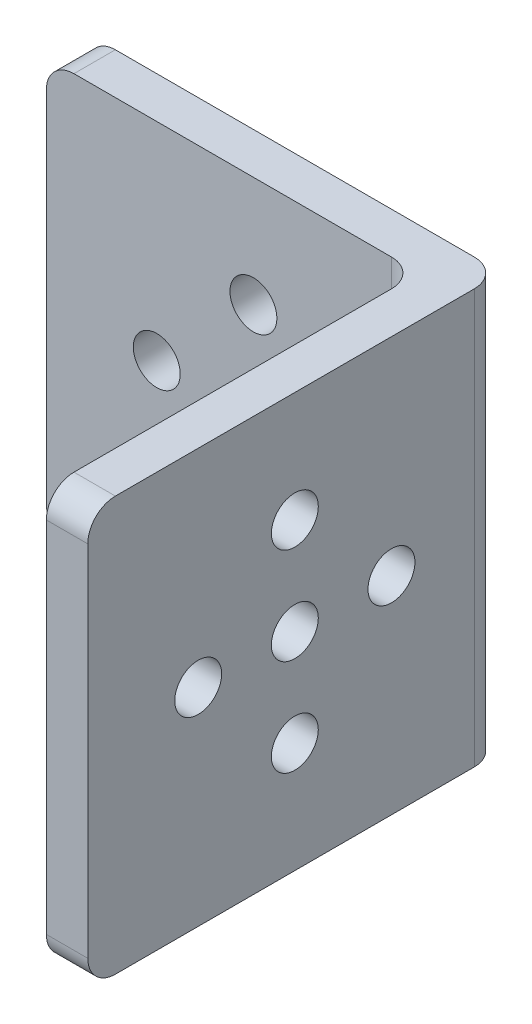
SolidWorks part; units mm, degrees
ref_plane "Front Plane" through (0, 0, 0) normal (0, 0, 1) x (1, 0, 0)
ref_plane "Top Plane" through (0, 0, 0) normal (0, 1, 0) x (1, 0, 0)
ref_plane "Right Plane" through (0, 0, 0) normal (1, 0, 0) x (0, 0, -1)
sketch "Sketch1" plane through (0, 0, 0) normal (0, 0, 1) x (1, 0, 0)
  line L0 (12, 15) -> (12, -15)
  line L9 (-15, -15) -> (15, -15)
  line L10 (-15, -15) -> (-15, 15)
  line L11 (-15, 15) -> (15, 15)
  line L12 (15, -15) -> (15, 15)
  line L13 (-15, -15) -> (15, 15) construction
  line L14 (-15, 15) -> (15, -15) construction
  point P0 (0, 0)
  dimension "D1" = 30
  dimension "D2" = 3
extrude "Boss-Extrude1" add sketch "Sketch1" along normal blind 3 contours L11 L10 L9 L0 region at (-1.5, 0, 0)
extrude "Boss-Extrude2" add sketch "Sketch1<3>" along normal blind 30 contours L9 L12 L11 L0 region at (13.5, 0, 0)
sketch "Sketch1<3>" plane through (0, 0, 0) normal (0, 0, 1) x (1, 0, 0) same geometry as "Sketch1"
sketch "Sketch2" plane through (0, 0, 3) normal (0, 0, 1) x (1, 0, 0)
  circle A0 centre (0, 0) radius 1.5
  circle A1 centre (0, 0) radius 7
  circle A2 centre (0, 7) radius 1.5
  circle A3 centre (7, 0) radius 1.5
  circle A4 centre (0, -7) radius 1.5
  circle A5 centre (-7, 0) radius 1.5
  dimension "D1" = 3
  dimension "D2" = 14
  dimension "D3" = 3
  dimension "D4" = 3
  dimension "D5" = 3
  dimension "D6" = 3
hole_wizard "M3 Clearance Hole1" positions "3DSketch1" profile "Sketch3" hole size "M3" standard "ISO" end condition up to next
sketch3d "3DSketch1"
  point P0 (0, 7, 3)
  point P3 (-7, 0, 3)
  point P6 (7, 0, 3)
  point P9 (0, -7, 3)
  point P13 (0, 0, 0)
  point P16 (0, 0, 3)
sketch "Sketch3" plane through (0, 7, 3) normal (1, 0, 0) x (0, -1, 0)
  line L0 (0, 0) -> (0, 3)
  line L1 (0, 3) -> (1.7, 3)
  line L2 (1.7, 3) -> (1.7, 0)
  line L5 (1.7, 0) -> (0, 0)
  line L11 (0, -6.35) -> (0, 107.95) construction
  dimension "Thru Hole Dia." = 3.4
  dimension "Thru Hole Depth" = 3
sketch "Sketch5" plane through (15, 0, 0) normal (1, 0, 0) x (0, 0, -1)
  line L0 (-15, 15) -> (-15, -15) construction
  line L1 (-30, 15) -> (0, 15) construction
  line L2 (-30, -15) -> (0, -15) construction
  line L3 (-30, 0) -> (0, 0) construction
  line L4 (-30, -15) -> (-30, 15) construction
  circle A0 centre (-15, 0) radius 1.5
  circle A1 centre (-15, 0) radius 7
  circle A2 centre (-15, 7) radius 1.5
  circle A3 centre (-8, 0) radius 1.5
  circle A4 centre (-15, -7) radius 1.5
  circle A5 centre (-22, 0) radius 1.5
  dimension "D1" = 3
  dimension "D2" = 14
  dimension "D3" = 3
  dimension "D4" = 3
  dimension "D5" = 3
  dimension "D6" = 3
hole_wizard "M3 Clearance Hole2" positions "3DSketch2" profile "Sketch6" hole size "M3" standard "ISO" end condition up to next
sketch3d "3DSketch2"
  point P0 (15, 7, 15)
  point P3 (15, 0, 22)
  point P6 (15, 0, 15)
  point P9 (15, 0, 8)
  point P12 (15, -7, 15)
sketch "Sketch6" plane through (15, 7, 15) normal (0, 1, 0) x (0, 0, -1)
  line L0 (0, 0) -> (0, 3)
  line L1 (0, 3) -> (1.7, 3)
  line L2 (1.7, 3) -> (1.7, 0)
  line L5 (1.7, 0) -> (0, 0)
  line L11 (0, -6.35) -> (0, 107.95) construction
  dimension "Thru Hole Dia." = 3.4
  dimension "Thru Hole Depth" = 3
fillet "Fillet1" radius 2 2 edges at (15, 0, 0) (12, 0, 3)
fillet "Fillet2" radius 2 4 edges at (-15, -15, 1.5) (-15, 15, 1.5) (13.5, 15, 30) (13.5, -15, 30)
